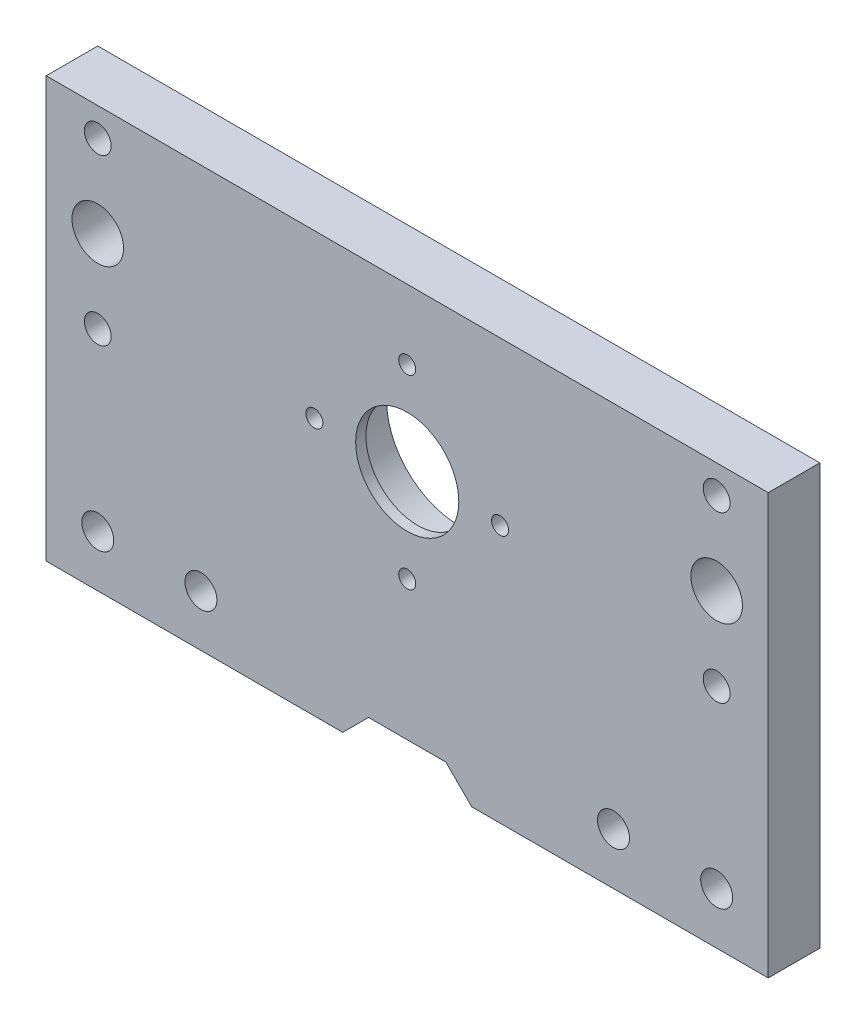
SolidWorks part; units mm, degrees
material "6061 Alloy"
ref_plane "Ön Düzlem" through (0, 0, 0) normal (0, 0, 1) x (1, 0, 0)
ref_plane "Üst Düzlem" through (0, 0, 0) normal (0, 1, 0) x (1, 0, 0)
ref_plane "Sağ Düzlem" through (0, 0, 0) normal (1, 0, 0) x (0, 0, -1)
sketch "Sketch1" plane through (0, 0, 0) normal (0, 0, 1) x (1, 0, 0)
  line L1 (-70, 40.75) -> (70, 40.75)
  line L2 (-70, 40.75) -> (-70, -40.75)
  line L3 (-70, -40.75) -> (70, -40.75)
  line L4 (70, 40.75) -> (70, -40.75)
  line L5 (-70, 40.75) -> (70, -40.75) construction
  line L6 (-70, -40.75) -> (70, 40.75) construction
  point P0 (0, 0)
  dimension "D1" = 81.5
  dimension "D2" = 140
extrude "Boss-Extrude1" add sketch "Sketch1" along normal blind 10
sketch "Sketch2" plane through (0, 0, 0) normal (0, 0, -1) x (-1, 0, 0)
  line L0 (0, 9.25) -> (0, 40.75) construction
  line L2 (-70, 40.75) -> (70, 40.75) construction
  circle A0 centre (0, 9.25) radius 14
  dimension "D1" = 31.5
  dimension "D4" = 28
extrude "Cut-Extrude2" cut sketch "Sketch2" against normal blind 8
sketch "Sketch5" plane through (0, 0, 0) normal (0, 0, -1) x (-1, 0, 0)
  line L0 (0, 9.25) -> (0, 19.25) construction
  line L1 (-60, 19.25) -> (60, 19.25) construction
  line L2 (70, 40.75) -> (70, -40.75) construction
  line L3 (-70, -40.75) -> (-70, 40.75) construction
  line L4 (70, -40.75) -> (-70, -40.75) construction
  circle A0 centre (-60, 19.25) radius 5
  circle A1 centre (60, 19.25) radius 5
  circle A2 centre (-60, 35.25) radius 2.6
  circle A3 centre (-60, 3.25) radius 2.6
  circle A4 centre (60, 35.25) radius 2.6
  circle A5 centre (60, 3.25) radius 2.6
  circle A6 centre (-60, -30.75) radius 3.1
  circle A7 centre (-40, -30.75) radius 3.1
  circle A8 centre (40, -30.75) radius 3.1
  circle A9 centre (60, -30.75) radius 3.1
  point P7 (0, 19.25)
  dimension "D3" = 10
  dimension "D4" = 5.2
  dimension "D5" = 32
  dimension "D6" = 16
  dimension "D7" = 16
  dimension "D8" = 16
  dimension "D9" = 10
  dimension "D10" = 10
  dimension "D11" = 10
  dimension "D12" = 10
  dimension "D13" = 6.2
  dimension "D14" = 10
  dimension "D15" = 20
  dimension "D16" = 20
  dimension "D17" = 10
  dimension "D18" = 10
  dimension "D19" = 10
  dimension "D1" = 10
  dimension "D2" = 120
extrude "Cut-Extrude4" cut sketch "Sketch5" against normal through all
sketch "Sketch25" plane through (0, 0, 10) normal (0, 0, 1) x (1, 0, 0)
  line L0 (-70, -40.75) -> (70, -40.75) construction
  line L2 (-17.5, -35.75) -> (17.5, -35.75)
  line L3 (-17.5, -35.75) -> (-17.5, -40.75)
  line L4 (-17.5, -40.75) -> (17.5, -40.75)
  line L5 (17.5, -35.75) -> (17.5, -40.75)
  point P0 (0, -40.75)
  dimension "D1" = 35
  dimension "D2" = 5
extrude "Cut-Extrude6" cut sketch "Sketch25" against normal through all
chamfer "Chamfer2" distance 10 angle 45 2 edges at (17.5, -35.75, 5) (-17.5, -35.75, 5)
sketch "Sketch27" plane through (0, 0, 8) normal (0, 0, -1) x (-1, 0, 0)
  circle A0 centre (0, 9.25) radius 10
  dimension "D1" = 20
extrude "Cut-Extrude8" cut sketch "Sketch27" against normal blind 3
sketch "Sketch28" plane through (0, 0, 0) normal (0, 0, -1) x (-1, 0, 0)
  line L0 (0, 9.25) -> (0, 27.25)
  dimension "D1" = 18
hole_wizard "M4 Tapped Hole1" positions "3DSketch1" profile "Sketch30" tap size "M4" standard "ISO"
sketch3d "3DSketch1"
  point P0 (0, 27.25, 0)
sketch "Sketch30" plane through (0, 27.25, 0) normal (1, 0, 0) x (0, 1, 0)
  line L0 (0, 0) -> (0, 11.0914)
  line L1 (0, 11.0914) -> (1.65, 10.1)
  line L2 (1.65, 10.1) -> (1.65, 0)
  line L5 (1.65, 0) -> (0, 0)
  line L10 (0, 11.0914) -> (-1.65, 10.1) construction
  line L11 (0, -6.35) -> (0, 107.95) construction
  dimension "Tap Drill Dia." = 3.3
  dimension "Tap Drill Depth" = 10.1
  dimension "Drill Angle" = 118
cosmetic thread "Hole Thread1" parameters "D1"=8, "D2"=4
pattern_circular "CirPattern1" count 4 every 90 about axis through (0, 9.25, 0) along (0, 0, -1) of "M4 Tapped Hole1"
cosmetic thread "Hole Thread2" parameters "D1"=8, "D2"=4
cosmetic thread "Hole Thread3" parameters "D1"=8, "D2"=4
cosmetic thread "Hole Thread4" parameters "D1"=8, "D2"=4
